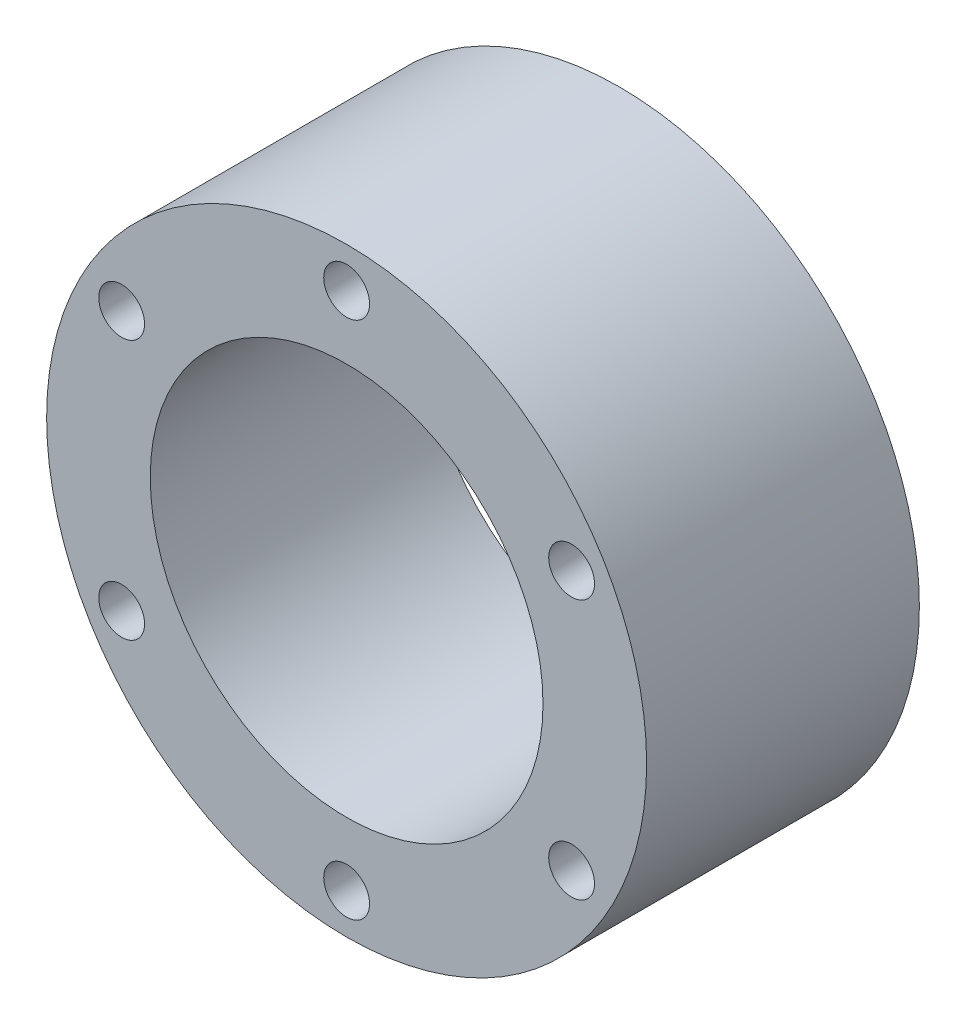
SolidWorks part; units mm, degrees
ref_plane "Front Plane" through (0, 0, 0) normal (0, 0, 1) x (1, 0, 0)
ref_plane "Top Plane" through (0, 0, 0) normal (0, 1, 0) x (1, 0, 0)
ref_plane "Right Plane" through (0, 0, 0) normal (1, 0, 0) x (0, 0, -1)
sketch "Sketch2" plane through (0, 0, 0) normal (0, 0, 1) x (1, 0, 0)
  circle A0 centre (0, 0) radius 27.5
  circle A1 centre (0, 0) radius 18
extrude "Boss-Extrude1" add sketch "Sketch2" along normal mid plane 25
hole_wizard "Tap Drill for M5x0.8 Tap1" positions "Sketch4" profile "Sketch3" hole size "M5x0.8" standard "ANSI Metric" end condition up to next
sketch "Sketch4" plane through (0, 0, -12.5) normal (0, 0, -1) x (-1, 0, 0)
  point P0 (0, 23.8125)
  dimension "D1" = 23.8125
sketch "Sketch3" plane through (0, 23.8125, -12.5) normal (1, 0, 0) x (0, 1, 0)
  line L0 (0, 0) -> (0, 25.001)
  line L1 (0, 25.001) -> (2.1, 25.001)
  line L2 (2.1, 25.001) -> (2.1, 0)
  line L5 (2.1, 0) -> (0, 0)
  line L11 (0, -6.35) -> (0, 107.95) construction
  dimension "Thru Hole Dia." = 4.2
  dimension "Thru Hole Depth" = 25.001
pattern_circular "CirPattern5" count 6 over 360 about axis through (0, 0, -12.5) along (0, 0, 1) of "Tap Drill for M5x0.8 Tap1"
ref_axis "Axis1" through (0, 0, 12.5) along (0, 0, -1)
